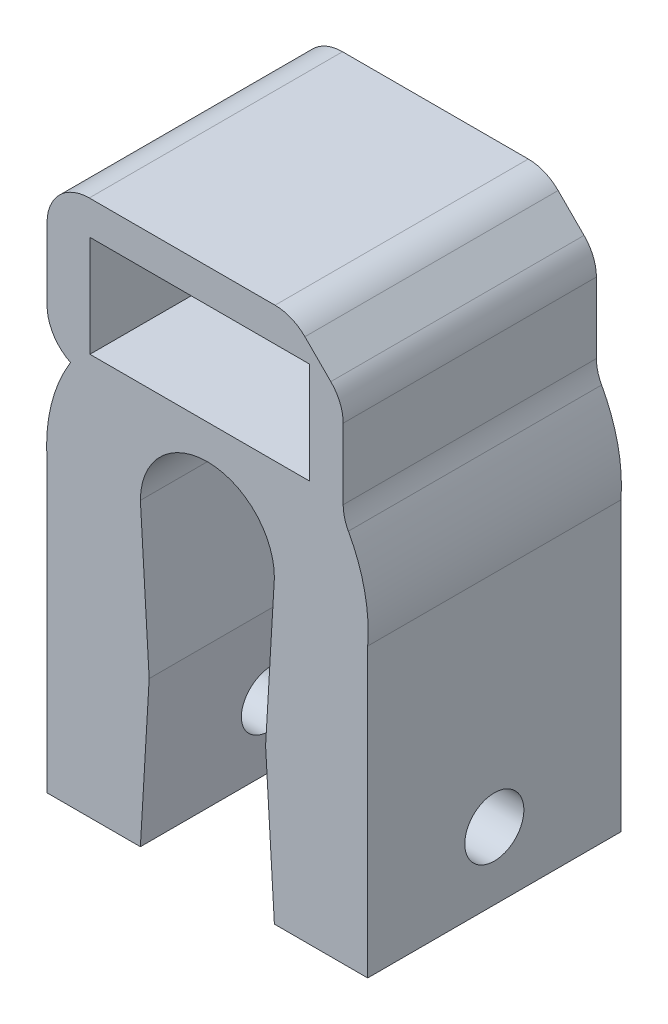
SolidWorks part; units mm, degrees
material "ABS PC"
ref_plane "Front Plane" through (0, 0, 0) normal (0, 0, 1) x (1, 0, 0)
ref_plane "Top Plane" through (0, 0, 0) normal (0, 1, 0) x (1, 0, 0)
ref_plane "Right Plane" through (0, 0, 0) normal (1, 0, 0) x (0, 0, -1)
ref_plane "New Front Plane" through (0, 0, 100) normal (0, 0, 1) x (1, 0, 0)
sketch "Sketch1" plane through (0, -100, 100) normal (0, 0, -1) x (1, 0, 0)
  line L0 (-3.4478, -91.1209) -> (-3.9688, -100)
  line L1 (-3.9688, -100) -> (3.9688, -100) construction
  line L2 (3.9688, -100) -> (3.4478, -91.1209)
  line L3 (-3.4478, -91.1209) -> (0, -91.1209) construction
  line L4 (0, -100) -> (0, -91.1209) construction
  line L5 (0, -91.1209) -> (3.4478, -91.1209) construction
  line L6 (-3.9688, -100) -> (-3.9688, -91.3412) construction
  line L7 (-3.9688, -91.3412) -> (-3.4608, -91.3412) construction
  line L8 (-3.9688, -100) -> (-9.4961, -100) construction
  line L9 (-9.4961, -100) -> (-9.4961, -99.2582) construction
  line L10 (9.4961, -99.2582) -> (9.4961, -82.2309)
  line L11 (9.4961, -99.2582) -> (9.4961, -100) construction
  line L12 (9.4961, -100) -> (3.9688, -100) construction
  line L13 (9.4961, -82.2309) -> (3.9688, -82.2309)
  line L14 (3.9688, -82.2309) -> (3.4478, -91.1209)
  line L15 (-3.9688, -82.2309) -> (-3.4478, -91.1209)
  line L16 (3.9688, -82.2309) -> (-3.9688, -82.2309) construction
  line L17 (-9.4961, -82.2309) -> (-9.4961, -99.2582)
  line L18 (-3.9688, -82.2309) -> (-9.4961, -82.2309)
  line L19 (3.4478, -91.1209) -> (9.4961, -91.1209) construction
  arc A0 (3.9688, -100) -> (-3.9688, -100) centre (0, -100) cw
  circle A1 centre (0, -100) radius 9.525 construction
  arc A2 (9.4961, -99.2582) -> (-9.4961, -99.2582) centre (0, -100) cw
  dimension "D1" = 3.9688
  dimension "D2" = 9.525
  dimension "D3" = 0.508
  dimension "D5" = 7.9375
  dimension "D6" = 8.89
extrude "Clip" add sketch "Sketch1" along normal blind 15
sketch "Sketch7" plane through (-9.4961, 0, 0) normal (-1, 0, 0) x (0, 0, 1)
  line L0 (100, -17.7691) -> (100, -0.7418) construction
  line L1 (85, -17.7691) -> (100, -17.7691) construction
  circle A0 centre (92.5, -13.7691) radius 1.75
  dimension "D1" = 3.5
  dimension "D2" = 7.5
  dimension "D3" = 4
extrude "Cut-Extrude4" cut sketch "Sketch7" against normal blind 19.812
sketch "Sketch8" plane through (0, 0, 100) normal (0, 0, 1) x (1, 0, 0)
  line L0 (-9.4961, 5) -> (8.0439, 5)
  line L1 (-9.4961, 5) -> (-9.4961, 14)
  line L2 (8.0439, 5) -> (8.0439, 14)
  line L3 (-9.4961, 14) -> (8.0439, 14)
  line L4 (-3.9688, -17.7691) -> (-9.4961, -17.7691) construction
  line L6 (-9.4961, -17.7691) -> (-9.4961, -0.7418) construction
  arc A2 (3.9688, 0) -> (-3.9688, 0) centre (0, 0) ccw construction
  dimension "D1" = 17.54
  dimension "D2" = 9
  dimension "D3" = 5
extrude "Boss-Extrude1" add sketch "Sketch8" against normal blind 15
sketch "Sketch10" plane through (0, 0, 85) normal (0, 0, -1) x (-1, 0, 0)
  line L0 (6.9561, 12) -> (6.9561, 6)
  line L1 (6.9561, 12) -> (-6.0439, 12)
  line L2 (6.9561, 6) -> (-6.0439, 6)
  line L3 (-6.0439, 12) -> (-6.0439, 6)
  line L4 (-8.0439, 14) -> (9.4961, 14) construction
  line L5 (-8.0439, 5.1011) -> (-8.0439, 14) construction
  dimension "D1" = 6
  dimension "D2" = 13
  dimension "D3" = 2
  dimension "D4" = 2
extrude "Cut-Extrude5" cut sketch "Sketch10" against normal blind 15
chamfer "Chamfer2" distance 3 angle 45 1 edges at (8.0439, 14, 92.5)
fillet "Fillet1" radius 2.5 5 edges at (8.0439, 5.1011, 92.5) (-9.4961, 14, 92.5) (-9.4961, 5, 92.5) (5.0439, 14, 92.5) (8.0439, 11, 92.5)
